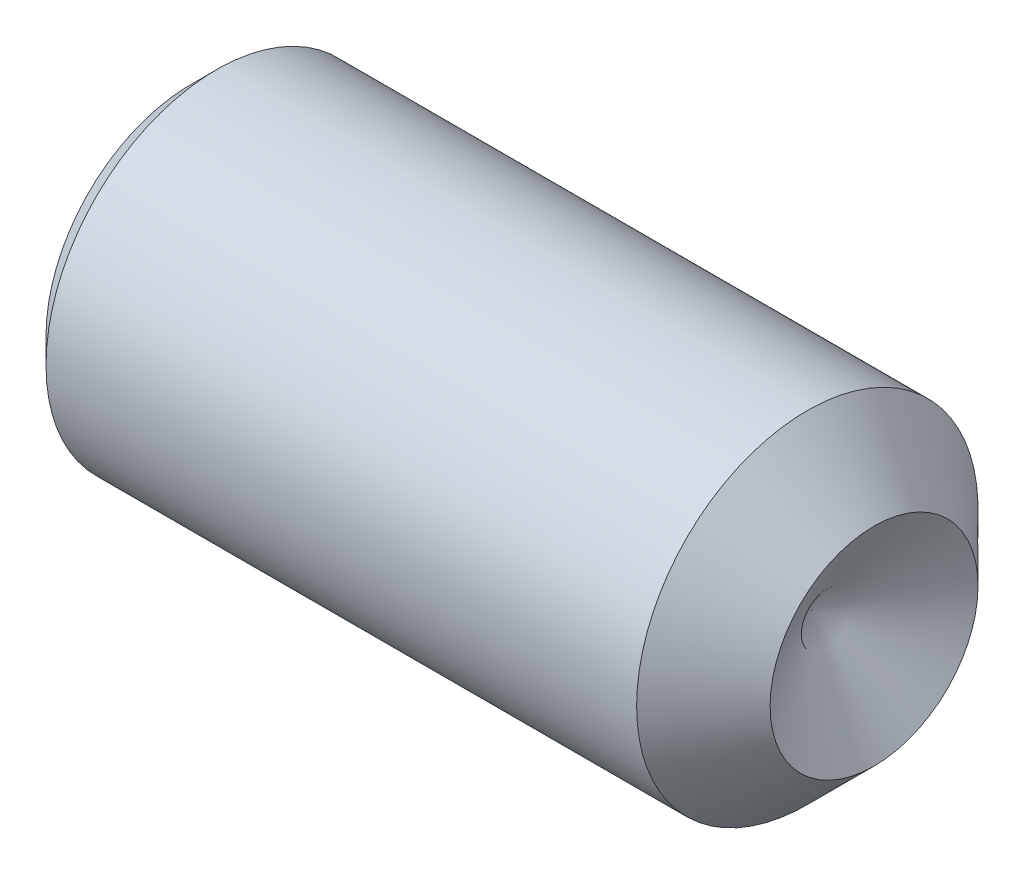
SolidWorks part; units mm, degrees
revolve "BaseBody" add sketch "BodySke" angle 360 about L5 other way angle 60
sketch "BodySke" plane through (0, 0, 0) normal (0, 0, 1) x (1, 0, 0)
  line L0 (0, 0) -> (0, 10.8102)
  line L1 (0, 10.8102) -> (1.8898, 12.7)
  line L2 (1.8898, 12.7) -> (45.8343, 12.7)
  line L3 (45.8343, 12.7) -> (50.8, 7.7343)
  line L4 (46.1528, 0) -> (0, 0)
  line L5 (-12.7, 0) -> (88.9, 0) construction
  line L6 (46.1528, 0) -> (50.8, 7.7343)
  line L7 (50.8, 7.7343) -> (50.8, 17.2593) construction
  line L8 (0, -10.8102) -> (1.8898, -12.7) construction
  line L9 (46.1528, 0) -> (50.8, -7.7343) construction
  line L10 (45.8343, -12.7) -> (50.8, -7.7343) construction
  line L11 (2.1082, 15.875) -> (2.1082, -3.175) construction
  dimension "Length" = 50.8
  dimension "Diameter" = 25.4
cosmetic thread "ThreadCosmetic" [suppressed] parameters "Thread_minor"=21.6205
ref_plane "Plane1" through (0, 0, 0) normal (0, 0, 1) x (1, 0, 0)
ref_plane "Plane2" through (0, 0, 0) normal (0, 1, 0) x (1, 0, 0)
ref_plane "Plane3" through (0, 0, 0) normal (1, 0, 0) x (0, 0, -1)
sketch "Sketch2" plane through (0, 0, 0) normal (-1, 0, 0) x (0, 0, 1)
  line L0 (4.1208, 7.1374) -> (-4.1208, 7.1374)
  line L1 (-4.1208, 7.1374) -> (-8.2416, 0)
  line L2 (4.1208, 7.1374) -> (8.2416, 0)
  line L3 (4.1208, -7.1374) -> (8.2416, 0)
  line L4 (4.1208, -7.1374) -> (-4.1208, -7.1374)
  line L5 (-4.1208, -7.1374) -> (-8.2416, 0)
  dimension "D2" = 7.1374
  dimension "D3" = 7.1374
extrude "Hex" cut sketch "Sketch2" against normal blind 14.2748
sketch "Sketch4" plane through (0, 4.7709, -0.5249) normal (-1, 0, 0) x (0, 0, 1)
  line L0 (0.5249, -4.7709) -> (10.6976, -4.7709)
  line L1 (0.5249, -4.7709) -> (6.6732, -1.2211) construction
  line L2 (0.5249, -4.7709) -> (5.6112, 4.0389)
  line L3 (8.9666, -2.6687) -> (10.2861, -1.9069)
  line L4 (6.5663, 1.4888) -> (7.8858, 2.2506)
  arc A0 (8.9666, -2.6687) -> (6.5663, 1.4888) centre (0.5249, -4.7709) ccw
  arc A1 (10.6976, -4.7709) -> (10.2861, -1.9069) centre (0.5249, -4.7709) ccw
  arc A2 (5.6112, 4.0389) -> (7.8858, 2.2506) centre (0.5249, -4.7709) cw
  circle A3 centre (0.5249, -4.7709) radius 8.6995 construction
  circle A4 centre (0.5249, -4.7709) radius 10.1727 construction
  dimension "Spline_n_dim" = 17.399
  dimension "Spline_m_dim" = 20.3454
  dimension "D1" = 30
  dimension "Spline_p_dim" = 4.8006
  dimension "D3" = 2.4003
extrude "Spline" [suppressed] cut sketch "Sketch4" against normal blind 12.7
pattern_circular "CirPattern1" [suppressed] count 6 every 60 about axis through (-12.7, 0, 0) along (1, 0, 0)
sketch "ThdSchSke" plane through (0, 0, 0) normal (0, 0, 1) x (1, 0, 0)
  line L0 (1.8898, -10.8102) -> (0.5665, -12.7)
  line L1 (1.8898, -10.8102) -> (3.213, -12.7)
  line L2 (3.213, -12.7) -> (3.213, -15.875)
  line L3 (-3.175, 0) -> (5.1513, 0) construction
  line L4 (1.8898, 12.7) -> (1.8898, -12.7) construction
  line L5 (3.213, -15.875) -> (0.5665, -15.875)
  line L6 (0.5665, -15.875) -> (0.5665, -12.7)
  dimension "Thread_minor" = 21.6205
  dimension "Diameter" = 25.4
revolve "ThreadSchematic" [suppressed] cut sketch "ThdSchSke" angle 360 about L3
pattern_linear "ThdSchPat" [suppressed]
equation "\"D2@Sketch2\" = \"Hex_size@Sketch2\" / 2"
equation "\"D3@Sketch2\" = \"Hex_size@Sketch2\" / 2"
equation "\"Thread_minor@ThreadCosmetic\" = \"Minor_dia@BodySke\""
equation "\"D1@Sketch4\" = \"Spline_a_dim@Sketch4\" / 2"
equation "\"D3@Sketch4\" = \"Spline_p_dim@Sketch4\" / 2"
equation "\"D2@CirPattern1\" = \"Spline_a_dim@Sketch4\""
equation "\"Num_teeth@CirPattern1\" = 360 / \"D2@CirPattern1\""
equation "\"Thread_minor@ThdSchSke\" = \"Thread_minor@ThreadCosmetic\""
equation "\"Diameter@ThdSchSke\" = \"Diameter@BodySke\""
equation "\"Overcut@ThdSchSke\" = \"Diameter@BodySke\" * 1.25"
equation "\"Num_threads@ThdSchPat\" = int( (\"Length@BodySke\" - ( ( ( \"Diameter@BodySke\" - \"Minor_dia@BodySke\" ) * 0.5 ) / tan( \"Drive_ch_ang@BodySke\" * 0.017453292 ) ) - ( ( ( \"Diameter@BodySke\" - \"Cup_dia@BodySke\" ) * 0.5 ) * tan( \"Cup_nose_ang@BodySke\" * 0.017453292 ) ) ) / \"Advance@BodySke\" + 0.999 )  + 1"
equation "\"Advance@ThdSchPat\" = (\"Length@BodySke\" - ( ( ( \"Diameter@BodySke\" - \"Minor_dia@BodySke\" ) * 0.5 ) / tan( \"Drive_ch_ang@BodySke\" * 0.017453292 ) ) - ( ( ( \"Diameter@BodySke\" - \"Cup_dia@BodySke\" ) * 0.5 ) * tan( \"Cup_nose_ang@BodySke\" * 0.017453292 ) ) ) /  (\"Num_threads@ThdSchPat\" - 1) 'relax it"
equation "' \"Num_threads@ThdSchPat\" = \"Num_threads@ThdSchPat\" - sgn( \"Num_threads@ThdSchPat\" - 1) '---chamfered tips only---"
